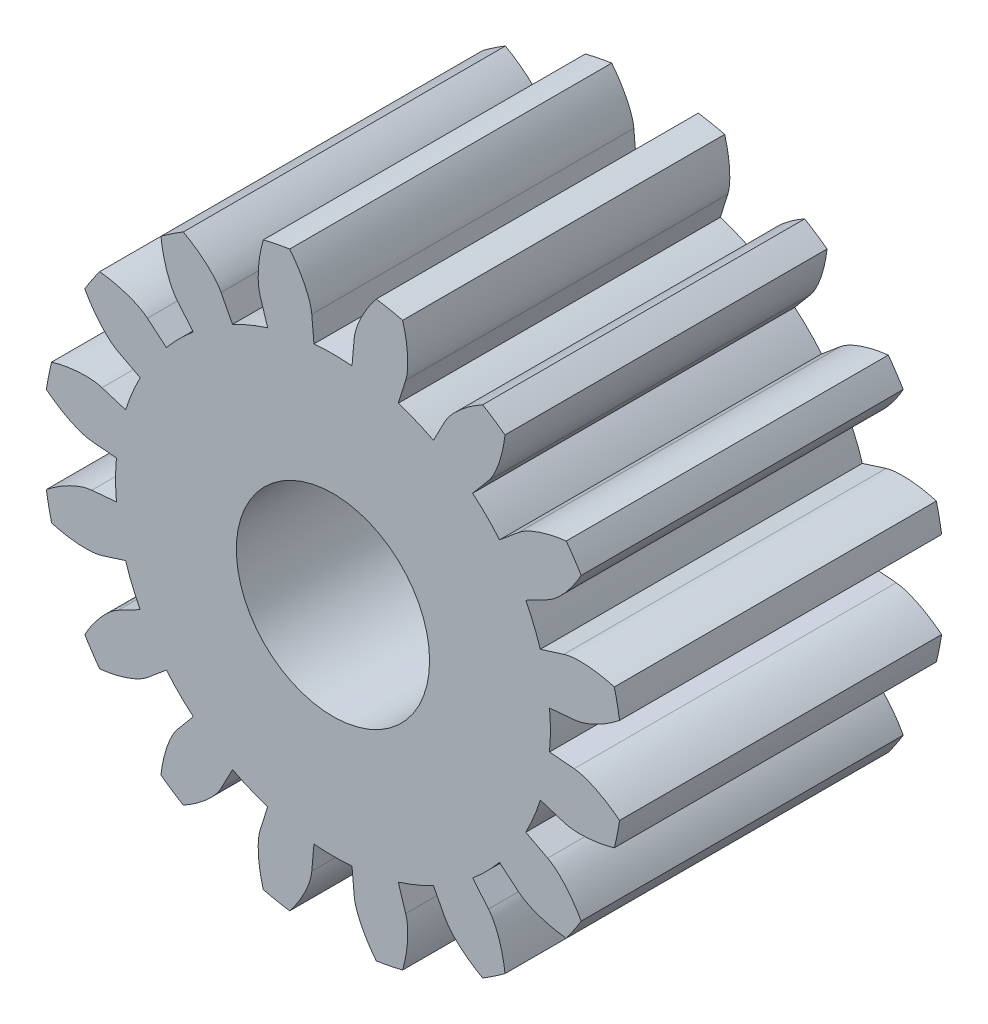
SolidWorks part; units mm, degrees
ref_plane "前视基准面" through (0, 0, 0) normal (0, 0, 1) x (1, 0, 0)
ref_plane "上视基准面" through (0, 0, 0) normal (0, 1, 0) x (1, 0, 0)
ref_plane "右视基准面" through (0, 0, 0) normal (1, 0, 0) x (0, 0, -1)
other "Configuration Table"
sketch "草图1" plane through (0, 0, 0) normal (0, 0, 1) x (1, 0, 0)
  line L0 (0, 0) -> (4, 0) construction
  line L1 (0, 0) -> (3.9807, 0.3921) construction
  line L2 (0, 0) -> (3.7443, 0.3291)
  line L3 (3.9807, 0.3921) -> (3.9807, -0.3921) construction
  line L4 (0, 0) -> (3.7443, -0.3291)
  circle A0 centre (0, 0) radius 4.5
  circle A1 centre (0, 0) radius 4 construction
  circle A2 centre (0, 0) radius 3.375
  circle A3 centre (0, 0) radius 3.7588 construction
  circle A4 centre (0, 0) radius 1.5
  spline S0 degree 4 poles (3.7443, 0.3291) (3.7729, 0.3316) (3.852, 0.3445) (3.9981, 0.3926) (4.2218, 0.5023) (4.4866, 0.6881) (4.7894, 0.9723) (5.0903, 1.3552) (5.3572, 1.8186) (5.6269, 2.4866) (5.7837, 3.1915) (5.8395, 3.939) (5.7839, 4.8292) (5.6145, 5.7064) (5.2709, 6.6864) (4.7256, 7.7028) (4.0402, 8.6299) (3.2362, 9.4556) (2.3338, 10.1718) (1.3511, 10.7732) (0.306, 11.2565) (-0.6502, 11.5751) (-1.4192, 11.7574) (-1.9866, 11.8556) (-2.3401, 11.9048) (-2.6306, 11.9368) (-2.9071, 11.9619) (-3.2112, 11.9792) (-3.4455, 11.9894) (-3.715, 11.9923) (-3.9867, 11.9914) (-4.2588, 11.9836) (-4.7357, 11.9589) (-5.1232, 11.9154) (-5.525, 11.8674) (-5.7188, 11.8311) (-5.8484, 11.8109) knots 0 0 0 0 0 0.005604 0.015718 0.02996 0.048734 0.068727 0.096889 0.125051 0.153212 0.209535 0.237696 0.271429 0.327752 0.384075 0.440398 0.496721 0.553044 0.609367 0.66569 0.722013 0.778336 0.806497 0.820578 0.834659 0.84874 0.86282 0.876901 0.890982 0.900036 0.909091 0.931818 0.954545 0.977273 1 1 1 1 1 construction
  spline S1 degree 4 poles (3.7443, 0.3291) (3.7729, 0.3316) (3.852, 0.3445) (3.9981, 0.3926) (4.2218, 0.5023) (4.4866, 0.6881) (4.7894, 0.9723) (5.0903, 1.3552) (5.3572, 1.8186) (5.6269, 2.4866) (5.7837, 3.1915) (5.8395, 3.939) (5.7839, 4.8292) (5.6145, 5.7064) (5.2709, 6.6864) (4.7256, 7.7028) (4.0402, 8.6299) (3.2362, 9.4556) (2.3338, 10.1718) (1.3511, 10.7732) (0.306, 11.2565) (-0.6502, 11.5751) (-1.4192, 11.7574) (-1.9866, 11.8556) (-2.3401, 11.9048) (-2.6306, 11.9368) (-2.9071, 11.9619) (-3.2112, 11.9792) (-3.4455, 11.9894) (-3.715, 11.9923) (-3.8743, 11.9918) (-3.9585, 11.9906) (-4.0005, 11.9898) knots 0 0 0 0 0 0.005604 0.015718 0.02996 0.048734 0.068727 0.096889 0.125051 0.153212 0.209535 0.237696 0.271429 0.327752 0.384075 0.440398 0.496721 0.553044 0.609367 0.66569 0.722013 0.778336 0.806497 0.820578 0.834659 0.84874 0.86282 0.876901 0.890982 0.900036 0.909091 0.909091 0.909091 0.909091 0.909091
  spline S2 degree 4 poles (3.7443, -0.3291) (3.7729, -0.3316) (3.852, -0.3445) (3.9981, -0.3926) (4.2218, -0.5023) (4.4866, -0.6881) (4.7894, -0.9723) (5.0903, -1.3552) (5.3572, -1.8186) (5.6269, -2.4866) (5.7837, -3.1915) (5.8395, -3.939) (5.7839, -4.8292) (5.6145, -5.7064) (5.2709, -6.6864) (4.7256, -7.7028) (4.0402, -8.6299) (3.2362, -9.4556) (2.3338, -10.1718) (1.3511, -10.7732) (0.306, -11.2565) (-0.6502, -11.5751) (-1.4192, -11.7574) (-1.9866, -11.8556) (-2.3401, -11.9048) (-2.6306, -11.9368) (-2.9071, -11.9619) (-3.2112, -11.9792) (-3.4455, -11.9894) (-3.715, -11.9923) (-3.9867, -11.9914) (-4.2588, -11.9836) (-4.7357, -11.9589) (-5.1232, -11.9154) (-5.525, -11.8674) (-5.7188, -11.8311) (-5.8484, -11.8109) knots 0 0 0 0 0 0.005604 0.015718 0.02996 0.048734 0.068727 0.096889 0.125051 0.153212 0.209535 0.237696 0.271429 0.327752 0.384075 0.440398 0.496721 0.553044 0.609367 0.66569 0.722013 0.778336 0.806497 0.820578 0.834659 0.84874 0.86282 0.876901 0.890982 0.900036 0.909091 0.931818 0.954545 0.977273 1 1 1 1 1 construction
  spline S3 degree 4 poles (3.7443, -0.3291) (3.7729, -0.3316) (3.852, -0.3445) (3.9981, -0.3926) (4.2218, -0.5023) (4.4866, -0.6881) (4.7894, -0.9723) (5.0903, -1.3552) (5.3572, -1.8186) (5.6269, -2.4866) (5.7837, -3.1915) (5.8395, -3.939) (5.7839, -4.8292) (5.6145, -5.7064) (5.2709, -6.6864) (4.7256, -7.7028) (4.0402, -8.6299) (3.2362, -9.4556) (2.3338, -10.1718) (1.3511, -10.7732) (0.306, -11.2565) (-0.6502, -11.5751) (-1.4192, -11.7574) (-1.9866, -11.8556) (-2.3401, -11.9048) (-2.6306, -11.9368) (-2.9071, -11.9619) (-3.2112, -11.9792) (-3.4455, -11.9894) (-3.715, -11.9923) (-3.8743, -11.9918) (-3.9585, -11.9906) (-4.0005, -11.9898) knots 0 0 0 0 0 0.005604 0.015718 0.02996 0.048734 0.068727 0.096889 0.125051 0.153212 0.209535 0.237696 0.271429 0.327752 0.384075 0.440398 0.496721 0.553044 0.609367 0.66569 0.722013 0.778336 0.806497 0.820578 0.834659 0.84874 0.86282 0.876901 0.890982 0.900036 0.909091 0.909091 0.909091 0.909091 0.909091
  point P15 (3.9807, 0)
  dimension "齿顶圆直径" = 9
  dimension "分度圆直径" = 8
  dimension "齿根圆直径" = 6.75
  dimension "基圆直径" = 7.5175
  dimension "内孔直径" = 3
  dimension "渐近线镜像线夹角" = 5.625
extrude "凸台-拉伸1" add sketch "草图1" along normal blind 5 contours A0 | A4
extrude "切除-拉伸1" cut sketch "草图1<3>" along normal through all contours A2 S3 A0 S1 region at (4.0116, 0, 0)
sketch "草图1<3>" plane through (0, 0, 0) normal (0, 0, 1) x (1, 0, 0) same geometry as "草图1"
pattern_circular "阵列(圆周)1" count 16 every 22.5 about axis through (0, 0, 5) along (0, 0, 1) of "切除-拉伸1"
sketch "草图2" plane through (0, 0, 0) normal (0, 1, 0) x (1, 0, 0)
  line L0 (3.6216, 0) -> (2.8803, 0) construction
  line L1 (-3.251, -5) -> (3.251, -5)
  line L2 (-3.251, -5) -> (-3.251, 0)
  line L3 (-3.251, 0) -> (3.251, 0)
  line L4 (3.251, -5) -> (3.251, 0)
  line L5 (-3.251, -5) -> (3.251, 0) construction
  line L6 (-3.251, 0) -> (3.251, -5) construction
  line L7 (-3.6216, -5) -> (-2.8803, -5) construction
  point P0 (0, -2.5)
  point P7 (0, 0)
  point P8 (0, 0)
  point P10 (-3.251, -5)
equation "\"m\"= 0.5'模数"
equation "\"z\"= 16'齿数"
equation "\"a\"= 20度'压力角"
equation "\"d\"= \"m\" * \"z\"'分度圆直径"
equation "\"da\"= ( \"z\" + 2 ) * \"m\"'齿顶圆直径"
equation "\"df\"= ( \"z\" - 2.5 ) * \"m\"'齿根圆直径"
equation "\"s\"= 0.5 * PI * \"m\"'分度圆齿厚"
equation "\"r\"= 0.38 * \"m\"'齿根圆角"
equation "\"B\"= 0.3 * \"d\"'齿厚"
equation "\"db\"= \"m\" * \"z\" * cos ( \"a\" )'基圆直径"
equation "\"rb\"= \"db\" / 2'基圆半径"
equation "\"齿顶圆直径@草图1\"= \"da\""
equation "\"分度圆直径@草图1\"= \"d\""
equation "\"齿根圆直径@草图1\"= \"df\""
equation "\"基圆直径@草图1\"= \"db\""
equation "\"渐近线镜像线夹角@草图1\"= 360 / 4 / \"z\""
equation "\"h\"= 5'齿轮厚度"
equation "\"ir\"= 3'内孔直径"
equation "\"内孔直径@草图1\"= \"ir\""
equation "\"齿轮厚@凸台-拉伸1\"= \"h\""
equation "\"齿轮夹角@阵列(圆周)1\"= 360 / \"z\""
equation "\"齿数@阵列(圆周)1\"= \"z\""
